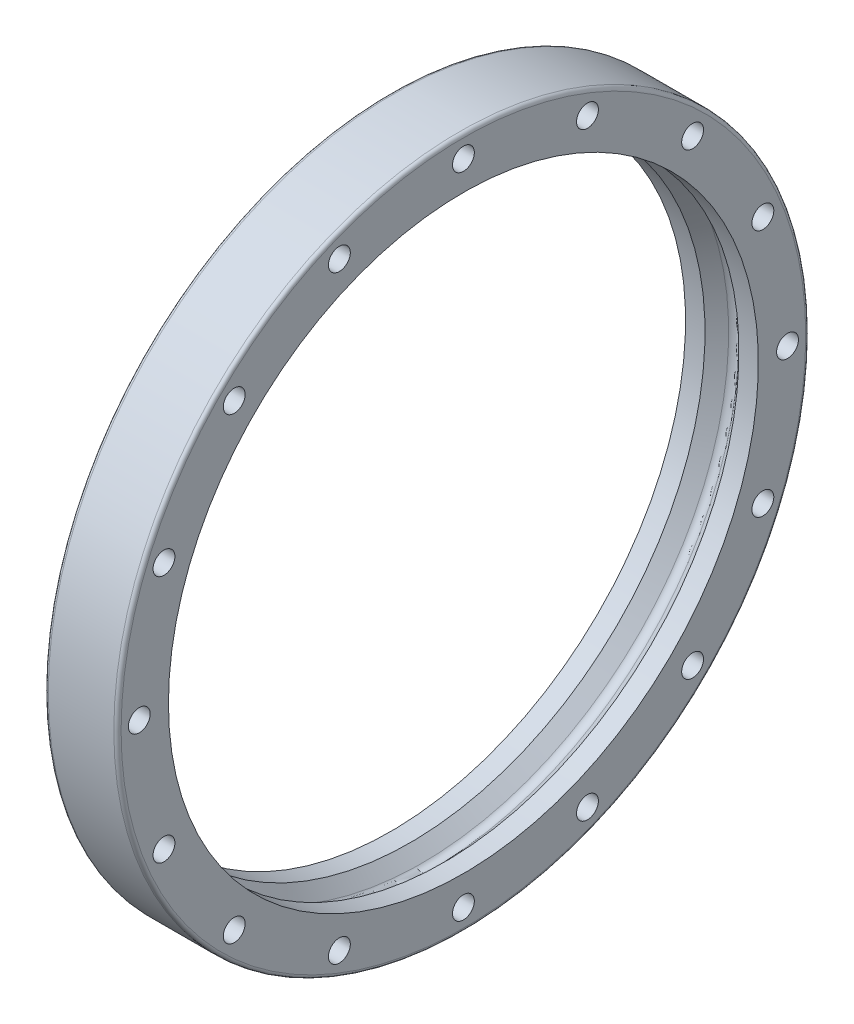
SolidWorks part; units mm, degrees
ref_plane "Front Plane" through (0, 0, 0) normal (0, 0, 1) x (1, 0, 0)
ref_plane "Top Plane" through (0, 0, 0) normal (0, 1, 0) x (1, 0, 0)
ref_plane "Right Plane" through (0, 0, 0) normal (1, 0, 0) x (0, 0, -1)
sketch "Sketch1" plane through (0, 0, 0) normal (0, 0, 1) x (1, 0, 0)
  line L0 (-42.0673, 0) -> (0, 0) construction
  line L1 (0, 0) -> (0, 88) construction
  line L2 (0, 85.6569) -> (5.6569, 80)
  line L3 (10, 95) -> (-10, 95)
  line L4 (10, 95) -> (10, 81)
  line L5 (10, 81) -> (-10, 81)
  line L6 (-10, 95) -> (-10, 81)
  line L7 (10, 95) -> (-10, 81) construction
  line L8 (10, 81) -> (-10, 95) construction
  line L9 (10, 79) -> (-10, 79)
  line L10 (10, 79) -> (10, 65)
  line L11 (10, 65) -> (-10, 65)
  line L12 (-10, 79) -> (-10, 65)
  line L13 (10, 79) -> (-10, 65) construction
  line L14 (10, 65) -> (-10, 79) construction
  line L15 (0, 85.6569) -> (-5.6569, 80)
  line L16 (5.6569, 80) -> (0, 74.3431)
  line L17 (-5.6569, 80) -> (0, 74.3431)
  line L18 (0, 85.6569) -> (0, 74.3431) construction
  line L19 (5.6569, 80) -> (-5.6569, 80) construction
  point P8 (0, 72)
  point P14 (0, 80)
  dimension "D1" = 20
  dimension "D2" = 65
  dimension "D3" = 95
  dimension "D4" = 14
  dimension "D5" = 1
  dimension "D6" = 8
revolve "Revolve1" add sketch "Sketch1" angle 360 about L0 region at (0, 88.4574, 0)
ref_axis "Axis1" through (10, 0, 0) along (-1, 0, 0)
fillet "Fillet1" radius 2 1 edges at (0, 0, 85.6569)
sketch "Sketch2" plane through (10, 0, 0) normal (1, 0, 0) x (0, 0, -1)
  circle A0 centre (0, 0) radius 89 construction
  circle A1 centre (0, 89) radius 3
  dimension "D1" = 6
  dimension "D2" = 178
extrude "Cut-Extrude1" cut sketch "Sketch2" against normal through all
pattern_circular "CirPattern1" count 16 over 360 about axis through (10, 0, 0) along (-1, 0, 0) of "Cut-Extrude1"
fillet "Fillet2" radius 1 2 edges at (10, 0, 95) (-10, 0, 95)
